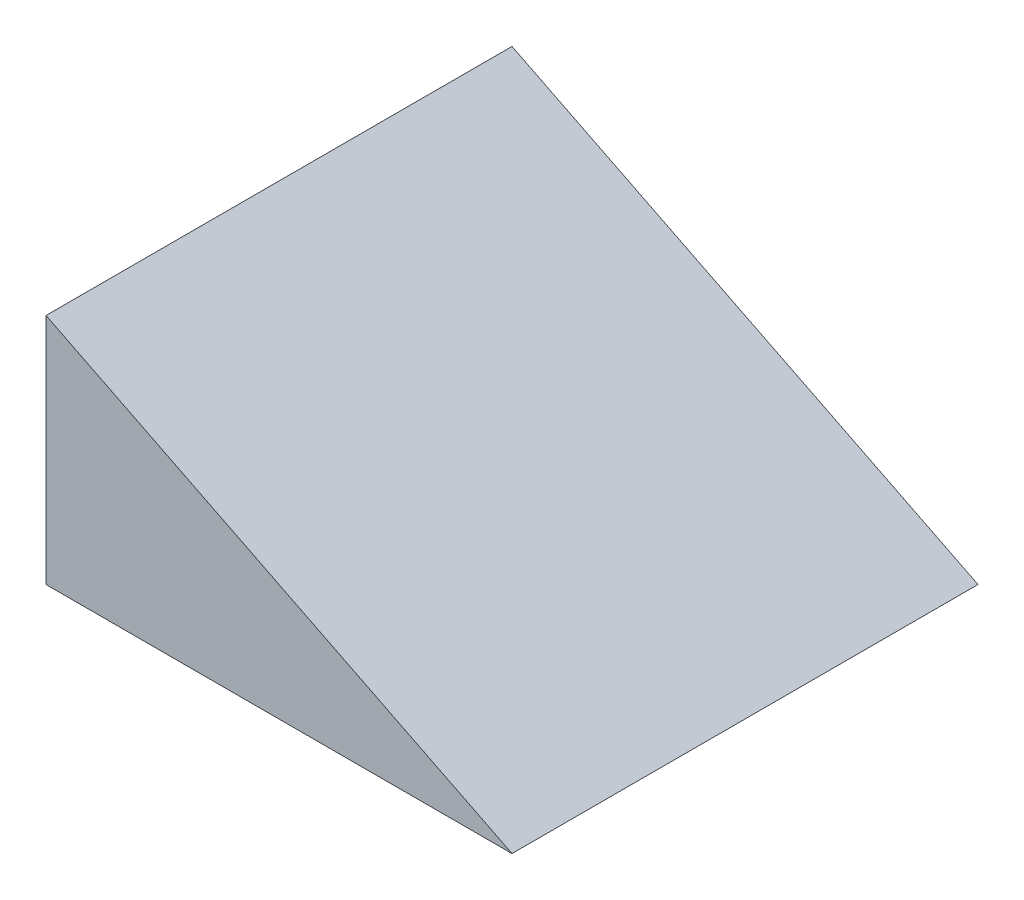
SolidWorks part; units mm, degrees
ref_plane "Front Plane" through (0, 0, 0) normal (0, 0, 1) x (1, 0, 0)
ref_plane "Top Plane" through (0, 0, 0) normal (0, 1, 0) x (1, 0, 0)
ref_plane "Right Plane" through (0, 0, 0) normal (1, 0, 0) x (0, 0, -1)
sketch "Sketch1" plane through (0, 0, 0) normal (0, 0, 1) x (1, 0, 0)
  line L0 (0, 0) -> (25.4, 0)
  line L1 (25.4, 0) -> (0, 12.7)
  line L2 (0, 12.7) -> (0, 0)
  dimension "D1" = 12.7
  dimension "D2" = 25.4
extrude "Boss-Extrude1" add sketch "Sketch1" along normal blind 12.7 and the other way blind 12.7
sketch "Sketch2" plane through (5.08, 10.16, 0) normal (0.4472, 0.8944, 0) x (0.8944, -0.4472, 0)
  line L0 (-5.6796, 0) -> (22.7185, 0)
  line L1 (-5.6796, 12.7) -> (-5.6796, -12.7) construction
  line L2 (22.7185, 12.7) -> (22.7185, -12.7) construction
  line L3 (8.5194, -12.7) -> (8.5194, 12.7)
  line L4 (22.7185, -12.7) -> (-5.6796, -12.7) construction
  line L5 (22.7185, 12.7) -> (-5.6796, 12.7) construction
  circle A1 centre (8.5194, 0) radius 2.3465
